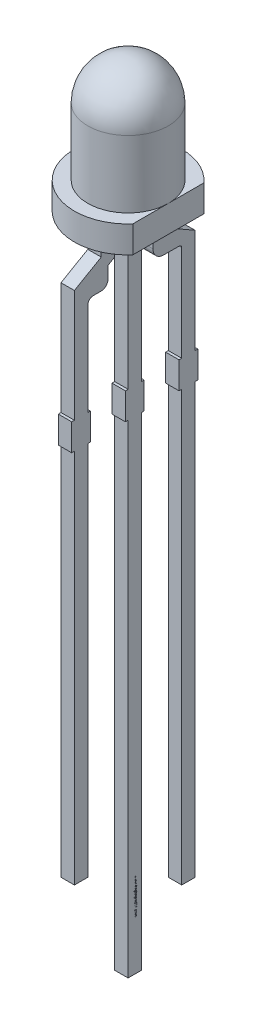
SolidWorks part; units mm, degrees
note: The reader was unsure of these and kept them because the rebuilt part matched: shared geometry of "Sketch2<3>".
ref_plane "Front Plane" through (0, 0, 0) normal (0, 0, 1) x (1, 0, 0)
ref_plane "Top Plane" through (0, 0, 0) normal (0, 1, 0) x (1, 0, 0)
ref_plane "Right Plane" through (0, 0, 0) normal (1, 0, 0) x (0, 0, -1)
sketch "Sketch1" plane through (0, 0, 0) normal (0, 1, 0) x (1, 0, 0)
  line L0 (1.5, 1.3229) -> (1.5, -1.3229)
  circle A0 centre (0, 0) radius 2
  circle A1 centre (0, 0) radius 1.5 construction
  dimension "D1" = 4
  dimension "D2" = 3
extrude "Extrude1" add sketch "Sketch1" along normal blind 1
sketch "Sketch2" plane through (0, 0, 0) normal (1, 0, 0) x (0, 0, -1)
  line L0 (0, 1) -> (0, 5)
  line L1 (1.3229, 1) -> (-1.3229, 1) construction
  line L2 (1.5, 3.5) -> (1.5, 1)
  line L3 (1.5, 1) -> (0, 1)
  line L4 (1.3229, 0) -> (-1.3229, 0) construction
  line L5 (1.1775, 0) -> (1.1775, -1)
  line L6 (1.1775, -1) -> (2.25, -1.6192)
  line L7 (2.25, -1.6192) -> (2.25, -22.5)
  line L8 (2.25, -22.5) -> (1.75, -22.5)
  line L9 (1.75, -22.5) -> (1.75, -1.93)
  line L10 (1.65, -1.83) -> (1.0775, -1.83)
  line L11 (0.6775, -1.43) -> (0.6775, 0)
  line L12 (0.6775, 0) -> (1.1775, 0)
  line L13 (-1.25, 0) -> (-1.25, -0.7334)
  line L14 (-0.25, 0) -> (0.25, 0)
  line L15 (-0.25, 0) -> (-0.25, -24.5)
  line L16 (-0.25, -24.5) -> (0.25, -24.5)
  line L17 (0.25, 0) -> (0.25, -24.5)
  line L18 (-2, 0) -> (2, 0) construction
  line L19 (-1.25, -0.7334) -> (-2.25, -1.3108)
  line L20 (-2.25, -1.3108) -> (-2.25, -20.5)
  line L21 (-2.25, -20.5) -> (-1.75, -20.5)
  line L22 (-1.75, -20.5) -> (-1.75, -2.03)
  line L23 (-1.55, -1.83) -> (-1.25, -1.83)
  line L24 (-0.75, -0.9833) -> (-1, -1.1277)
  line L25 (-1, -1.1277) -> (-1, -1.58)
  line L26 (-0.75, -0.9833) -> (-0.75, 0)
  line L27 (-0.75, 0) -> (-1.25, 0)
  line L28 (2, -22.5) -> (2, -7.5342) construction
  line L29 (-2, -5.5) -> (-2, -6.5) construction
  line L30 (0, -24.5) -> (0, -6.5616) construction
  line L31 (-2.35, -5.5) -> (-1.65, -5.5)
  line L32 (-2, -20.5) -> (-2, -6.3531) construction
  line L33 (-2.35, -5.5) -> (-2.35, -6.5)
  line L34 (-2.35, -6.5) -> (-1.65, -6.5)
  line L35 (-1.65, -5.5) -> (-1.65, -6.5)
  line L36 (0.9275, 0) -> (0.9275, -0.7786) construction
  line L37 (0, 0) -> (0, -0.5919) construction
  line L38 (-1.75, -3.6184) -> (-0.25, -3.6184) construction
  line L39 (0.25, -3.6184) -> (1.75, -3.6184) construction
  line L40 (-1, -3.6184) -> (-1, -5) construction
  line L41 (1, -3.6184) -> (1, -4.79) construction
  line L42 (0.35, -5.5) -> (0.35, -6.5)
  line L43 (0.35, -6.5) -> (-0.35, -6.5)
  line L44 (-0.35, -5.5) -> (-0.35, -6.5)
  line L45 (0.35, -5.5) -> (-0.35, -5.5)
  line L46 (1.65, -6.5) -> (2.35, -6.5)
  line L47 (2.35, -5.5) -> (2.35, -6.5)
  line L48 (1.65, -5.5) -> (1.65, -6.5)
  line L49 (1.65, -5.5) -> (2.35, -5.5)
  arc A0 (0, 5) -> (1.5, 3.5) centre (0, 3.5) cw
  arc A1 (0.6775, -1.43) -> (1.0775, -1.83) centre (1.0775, -1.43) ccw
  arc A2 (1.75, -1.93) -> (1.65, -1.83) centre (1.65, -1.93) ccw
  arc A3 (-1.55, -1.83) -> (-1.75, -2.03) centre (-1.55, -2.03) ccw
  arc A4 (-1, -1.58) -> (-1.25, -1.83) centre (-1.25, -1.58) cw
  dimension "D1" = 3
  dimension "D12" = 2
  dimension "D13" = 2
  dimension "D14" = 0.2
  dimension "D7" = 0.25
  dimension "D18" = 0.1
  dimension "D19" = 0.4
  dimension "D2" = 5
  dimension "D3" = 6.83
  dimension "D4" = 120
  dimension "D5" = 120
  dimension "D6" = 0.5
  dimension "D8" = 0.5
  dimension "D9" = 1
  dimension "D10" = 0.5
  dimension "D11" = 0.5
  dimension "D15" = 1
  dimension "D16" = 0.7
  dimension "D17" = 10.5
  dimension "D20" = 0.5725
  dimension "D21" = 24.5
  dimension "D22" = 2
  dimension "D23" = 4
  dimension "D24" = 0.7334
revolve "Revolve1" add sketch "Sketch2" angle 360 about L0
extrude "Extrude2" add sketch "Sketch2<3>" along normal mid plane 0.5
sketch "Sketch2<3>" plane through (0, 0, 0) normal (1, 0, 0) x (0, 0, -1) same geometry as "Sketch2"
sketch "Sketch3" plane through (0.25, 0, 0) normal (1, 0, 0) x (0, 0, -1)
  line L0 (0, -24.5) -> (0, -19.5) construction
  line L1 (0.25, -24.5) -> (-0.25, -24.5) construction
  text T0 "www.KingbrightUSA.com" font "Century Gothic" height 0.08
  dimension "D1" = 5
extrude "Cut-Extrude1" cut sketch "Sketch3" against normal blind 0.01
